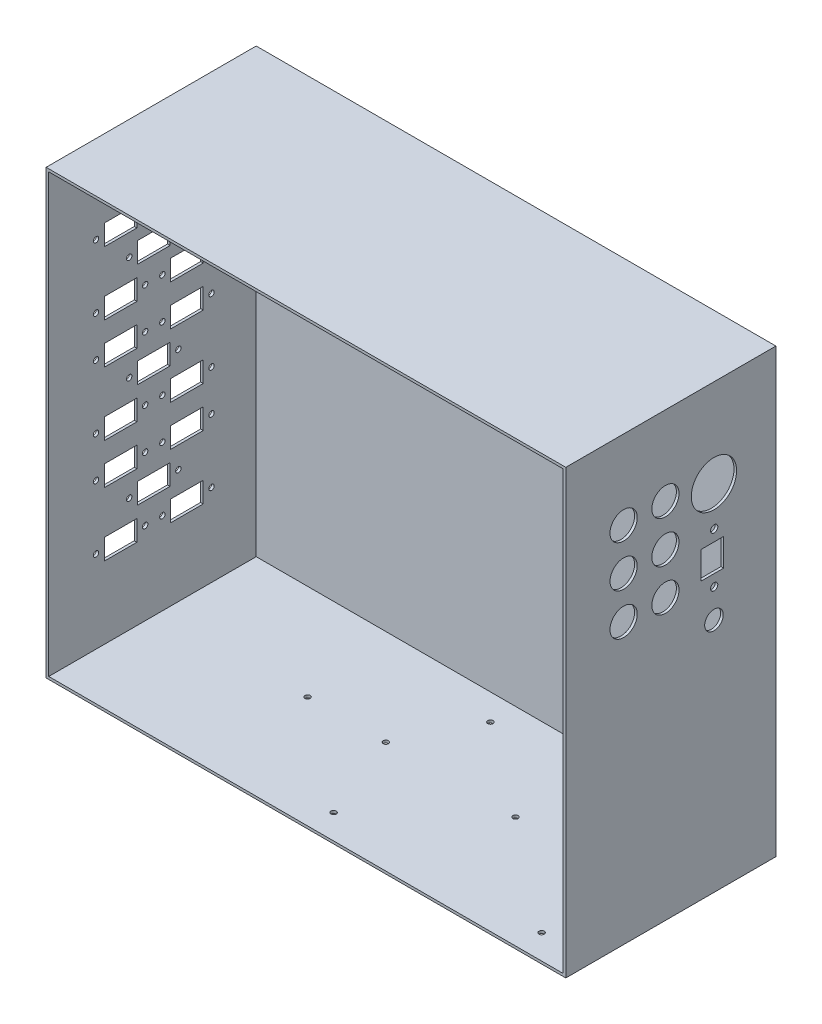
SolidWorks part; units mm, degrees
ref_plane "Front Plane" through (0, 0, 0) normal (0, 0, 1) x (1, 0, 0)
ref_plane "Top Plane" through (0, 0, 0) normal (0, 1, 0) x (1, 0, 0)
ref_plane "Right Plane" through (0, 0, 0) normal (1, 0, 0) x (0, 0, -1)
sketch "Sketch2" plane through (0, 0, 0) normal (0, 0, 1) x (1, 0, 0)
  line L1 (-149.225, 127) -> (149.225, 127)
  line L2 (-149.225, 127) -> (-149.225, -127)
  line L3 (-149.225, -127) -> (149.225, -127)
  line L4 (149.225, 127) -> (149.225, -127)
  line L5 (-149.225, 127) -> (149.225, -127) construction
  line L6 (-149.225, -127) -> (149.225, 127) construction
  point P0 (0, 0)
  dimension "D1" = 298.45
  dimension "D2" = 254
extrude "Boss-Extrude1" add sketch "Sketch2" along normal blind 120.65
shell "Shell1" thickness 1.5 removed face at (0, 0, 120.65)
sketch "Sketch3" plane through (149.225, 0, 0) normal (1, 0, 0) x (0, 0, -1)
  line L0 (-40.4352, 50.2841) -> (-40.4352, 57.3961) construction
  line L1 (-24.3484, 28.5671) -> (-24.2403, 50.2841) construction
  line L2 (-101.6, 95.7164) -> (-19.05, 95.7164) construction
  line L3 (-101.6, 95.7164) -> (-101.6, -88.9) construction
  line L4 (-101.6, -88.9) -> (-19.05, -88.9) construction
  line L5 (-19.05, 95.7164) -> (-19.05, -88.9) construction
  line L6 (-24.3484, 28.5671) -> (-30.4022, 28.5671) construction
  line L7 (-46.489, 28.5671) -> (-46.5749, 50.2841) construction
  line L8 (-24.2403, 50.2841) -> (-30.4022, 50.2841) construction
  line L9 (-30.4022, 50.2841) -> (-30.4022, 57.4161) construction
  line L10 (-40.4352, 28.5671) -> (-46.489, 28.5671) construction
  line L11 (-40.4352, 21.4551) -> (-40.4352, 28.5671) construction
  line L12 (-40.4352, 21.4551) -> (-30.4022, 21.4551) construction
  line L13 (-30.4022, 21.4551) -> (-30.4022, 28.5671) construction
  line L14 (-40.4352, 57.3961) -> (-30.4022, 57.4161) construction
  line L15 (-40.4352, 50.2841) -> (-46.5749, 50.2841) construction
  line L16 (-46.532, 39.4256) -> (-24.2943, 39.4256) construction
  line L17 (-35.4187, 23.6) -> (-35.4187, 57.4061) construction
  line L18 (-43.0873, 31.5516) -> (-43.0873, 47.2996)
  line L19 (-43.0873, 31.5516) -> (-30.0063, 31.5516)
  line L20 (-30.0063, 31.5516) -> (-30.0063, 47.2996)
  line L21 (-43.0873, 47.2996) -> (-30.0063, 47.2996)
  line L24 (-120.65, -127) -> (-120.65, 127) construction
  line L25 (-120.65, -127) -> (0, -127) construction
  circle A0 centre (-87.4395, 33.5559) radius 7.8105
  circle A1 centre (-63.4395, 33.5559) radius 7.8105
  circle A2 centre (-63.4395, 57.5559) radius 7.8105
  circle A3 centre (-63.4395, 81.5559) radius 7.8105
  circle A4 centre (-87.4395, 57.5559) radius 7.8105
  circle A5 centre (-87.4395, 81.5559) radius 7.8105
  circle A6 centre (-35.4187, 25.0111) radius 2.0638
  circle A7 centre (-35.4187, 53.8401) radius 2.0638
  circle A8 centre (-35.56, 8.5011) radius 5.334
  circle A9 centre (-35.56, 76.3489) radius 13.0175
  point P46 (-35.56, -18.9197)
  point P47 (0, 0)
  dimension "D1" = 15.621
  dimension "D4" = 82.55
  dimension "D5" = 14.1605
  dimension "D7" = 19.3675
  dimension "D10" = 28.829
  dimension "D11" = 6.5405
  dimension "D21" = 16.51
  dimension "D6" = 14.1605
  dimension "D8" = 0.512
  dimension "D9" = 13.081
  dimension "D12" = 21.717
  dimension "D13" = 15.748
  dimension "D14" = 7.6686
  dimension "D15" = 0.285
  dimension "D16" = 10.033
  dimension "D17" = 0.227
  dimension "D18" = 16.51
  dimension "D19" = 19.05
  dimension "D20" = 38.1
  dimension "D22" = 0.115
  dimension "D23" = 6.1397
  dimension "D24" = 16.51
  dimension "D2" = 2
  dimension "D3" = 3
extrude "PT Connector Cutouts" cut sketch "Sketch3" against normal up to next
sketch "Sketch4" plane through (-149.225, 0, 0) normal (-1, 0, 0) x (0, 0, 1)
  line L0 (41.275, 72.2563) -> (41.275, 84.0563) construction
  line L1 (31.925, 84.0563) -> (31.925, 72.2563)
  line L2 (31.925, 84.0563) -> (50.625, 84.0563)
  line L3 (50.625, 84.0563) -> (50.625, 72.2563)
  line L4 (31.925, 72.2563) -> (50.625, 72.2563)
  line L10 (22.225, -88.9) -> (98.425, -88.9) construction
  line L11 (22.225, -88.9) -> (22.225, 88.9) construction
  line L12 (22.225, 88.9) -> (98.425, 88.9) construction
  line L13 (98.425, -88.9) -> (98.425, 88.9) construction
  line L73 (120.65, 127) -> (0, 127) construction
  line L74 (0, 127) -> (0, -127) construction
  line L75 (31.925, 86.0563) -> (27.1625, 84.0563) construction
  line L81 (31.925, 70.2563) -> (50.625, 70.2563) construction
  line L83 (31.925, 86.0563) -> (50.625, 86.0563) construction
  line L84 (50.625, 86.0563) -> (55.3875, 84.0563) construction
  line L85 (31.925, 70.2563) -> (27.1625, 72.2563) construction
  line L86 (50.625, 70.2563) -> (55.3875, 72.2563) construction
  line L87 (31.925, 84.0563) -> (50.625, 84.0563) construction
  line L89 (31.925, 72.2563) -> (50.625, 72.2563) construction
  line L91 (31.925, 84.0563) -> (50.625, 84.0563) construction
  line L92 (24.275, 72.2563) -> (24.275, 84.0563) construction
  line L93 (24.275, 72.2563) -> (27.1625, 72.2563) construction
  line L94 (58.275, 72.2563) -> (58.275, 84.0563) construction
  line L95 (24.275, 84.0563) -> (27.1625, 84.0563) construction
  line L98 (55.3875, 84.0563) -> (58.275, 84.0563) construction
  line L99 (55.3875, 72.2563) -> (58.275, 72.2563) construction
  line L100 (31.925, 72.2563) -> (50.625, 72.2563) construction
  line L170 (120.65, -127) -> (0, -127) construction
  line L171 (70.025, 84.0563) -> (70.025, 72.2563)
  line L172 (70.025, 84.0563) -> (88.725, 84.0563)
  line L173 (88.725, 84.0563) -> (88.725, 72.2563)
  line L174 (70.025, 72.2563) -> (88.725, 72.2563)
  line L175 (79.375, 72.2563) -> (79.375, 84.0563) construction
  line L176 (70.025, 86.0563) -> (65.2625, 84.0563) construction
  line L177 (70.025, 70.2563) -> (88.725, 70.2563) construction
  line L178 (70.025, 86.0563) -> (88.725, 86.0563) construction
  line L179 (88.725, 86.0563) -> (93.4875, 84.0563) construction
  line L180 (70.025, 70.2563) -> (65.2625, 72.2563) construction
  line L181 (88.725, 70.2563) -> (93.4875, 72.2563) construction
  line L182 (70.025, 84.0563) -> (88.725, 84.0563) construction
  line L183 (70.025, 72.2563) -> (88.725, 72.2563) construction
  line L184 (70.025, 84.0563) -> (88.725, 84.0563) construction
  line L185 (62.375, 72.2563) -> (62.375, 84.0563) construction
  line L186 (62.375, 72.2563) -> (65.2625, 72.2563) construction
  line L187 (96.375, 72.2563) -> (96.375, 84.0563) construction
  line L188 (62.375, 84.0563) -> (65.2625, 84.0563) construction
  line L189 (93.4875, 84.0563) -> (96.375, 84.0563) construction
  line L190 (93.4875, 72.2563) -> (96.375, 72.2563) construction
  line L191 (70.025, 72.2563) -> (88.725, 72.2563) construction
  line L213 (70.025, 47.5438) -> (70.025, 35.7438)
  line L214 (70.025, 47.5438) -> (88.725, 47.5438)
  line L215 (88.725, 47.5438) -> (88.725, 35.7438)
  line L216 (70.025, 35.7438) -> (88.725, 35.7438)
  line L217 (79.375, 35.7438) -> (79.375, 47.5438) construction
  line L218 (70.025, 49.5438) -> (65.2625, 47.5438) construction
  line L219 (70.025, 33.7438) -> (88.725, 33.7438) construction
  line L220 (70.025, 49.5438) -> (88.725, 49.5438) construction
  line L221 (88.725, 49.5438) -> (93.4875, 47.5438) construction
  line L222 (70.025, 33.7438) -> (65.2625, 35.7438) construction
  line L223 (88.725, 33.7438) -> (93.4875, 35.7438) construction
  line L224 (70.025, 47.5438) -> (88.725, 47.5438) construction
  line L225 (70.025, 35.7438) -> (88.725, 35.7438) construction
  line L226 (70.025, 47.5438) -> (88.725, 47.5438) construction
  line L227 (62.375, 35.7438) -> (62.375, 47.5438) construction
  line L228 (62.375, 35.7438) -> (65.2625, 35.7438) construction
  line L229 (96.375, 35.7438) -> (96.375, 47.5438) construction
  line L230 (62.375, 47.5438) -> (65.2625, 47.5438) construction
  line L231 (93.4875, 47.5438) -> (96.375, 47.5438) construction
  line L232 (93.4875, 35.7438) -> (96.375, 35.7438) construction
  line L233 (70.025, 35.7438) -> (88.725, 35.7438) construction
  line L234 (70.025, 24.1563) -> (70.025, 12.3563)
  line L235 (70.025, 24.1563) -> (88.725, 24.1563)
  line L236 (88.725, 24.1563) -> (88.725, 12.3563)
  line L237 (70.025, 12.3563) -> (88.725, 12.3563)
  line L238 (79.375, 12.3563) -> (79.375, 24.1563) construction
  line L239 (70.025, 26.1563) -> (65.2625, 24.1563) construction
  line L240 (70.025, 10.3563) -> (88.725, 10.3563) construction
  line L241 (70.025, 26.1563) -> (88.725, 26.1563) construction
  line L242 (88.725, 26.1563) -> (93.4875, 24.1563) construction
  line L243 (70.025, 10.3563) -> (65.2625, 12.3563) construction
  line L244 (88.725, 10.3563) -> (93.4875, 12.3563) construction
  line L245 (70.025, 24.1563) -> (88.725, 24.1563) construction
  line L246 (70.025, 12.3563) -> (88.725, 12.3563) construction
  line L247 (70.025, 24.1563) -> (88.725, 24.1563) construction
  line L248 (62.375, 12.3563) -> (62.375, 24.1563) construction
  line L249 (62.375, 12.3563) -> (65.2625, 12.3563) construction
  line L250 (96.375, 12.3563) -> (96.375, 24.1563) construction
  line L251 (62.375, 24.1563) -> (65.2625, 24.1563) construction
  line L252 (93.4875, 24.1563) -> (96.375, 24.1563) construction
  line L253 (93.4875, 12.3563) -> (96.375, 12.3563) construction
  line L254 (70.025, 12.3563) -> (88.725, 12.3563) construction
  line L276 (70.025, -12.3562) -> (70.025, -24.1562)
  line L277 (70.025, -12.3562) -> (88.725, -12.3562)
  line L278 (88.725, -12.3562) -> (88.725, -24.1562)
  line L279 (70.025, -24.1562) -> (88.725, -24.1562)
  line L280 (79.375, -24.1562) -> (79.375, -12.3562) construction
  line L281 (70.025, -10.3562) -> (65.2625, -12.3562) construction
  line L282 (70.025, -26.1562) -> (88.725, -26.1562) construction
  line L283 (70.025, -10.3562) -> (88.725, -10.3562) construction
  line L284 (88.725, -10.3562) -> (93.4875, -12.3562) construction
  line L285 (70.025, -26.1562) -> (65.2625, -24.1562) construction
  line L286 (88.725, -26.1562) -> (93.4875, -24.1562) construction
  line L287 (70.025, -12.3562) -> (88.725, -12.3562) construction
  line L288 (70.025, -24.1562) -> (88.725, -24.1562) construction
  line L289 (70.025, -12.3562) -> (88.725, -12.3562) construction
  line L290 (62.375, -24.1562) -> (62.375, -12.3562) construction
  line L291 (62.375, -24.1562) -> (65.2625, -24.1562) construction
  line L292 (96.375, -24.1562) -> (96.375, -12.3562) construction
  line L293 (62.375, -12.3562) -> (65.2625, -12.3562) construction
  line L294 (93.4875, -12.3562) -> (96.375, -12.3562) construction
  line L295 (93.4875, -24.1562) -> (96.375, -24.1562) construction
  line L296 (70.025, -24.1562) -> (88.725, -24.1562) construction
  line L297 (70.025, -35.7437) -> (70.025, -47.5437)
  line L298 (70.025, -35.7437) -> (88.725, -35.7437)
  line L299 (88.725, -35.7437) -> (88.725, -47.5437)
  line L300 (70.025, -47.5437) -> (88.725, -47.5437)
  line L301 (79.375, -47.5437) -> (79.375, -35.7437) construction
  line L302 (70.025, -33.7437) -> (65.2625, -35.7437) construction
  line L303 (70.025, -49.5437) -> (88.725, -49.5437) construction
  line L304 (70.025, -33.7437) -> (88.725, -33.7437) construction
  line L305 (88.725, -33.7437) -> (93.4875, -35.7437) construction
  line L306 (70.025, -49.5437) -> (65.2625, -47.5437) construction
  line L307 (88.725, -49.5437) -> (93.4875, -47.5437) construction
  line L308 (70.025, -35.7437) -> (88.725, -35.7437) construction
  line L309 (70.025, -47.5437) -> (88.725, -47.5437) construction
  line L310 (70.025, -35.7437) -> (88.725, -35.7437) construction
  line L311 (62.375, -47.5437) -> (62.375, -35.7437) construction
  line L312 (62.375, -47.5437) -> (65.2625, -47.5437) construction
  line L313 (96.375, -47.5437) -> (96.375, -35.7437) construction
  line L314 (62.375, -35.7437) -> (65.2625, -35.7437) construction
  line L315 (93.4875, -35.7437) -> (96.375, -35.7437) construction
  line L316 (93.4875, -47.5437) -> (96.375, -47.5437) construction
  line L317 (70.025, -47.5437) -> (88.725, -47.5437) construction
  line L339 (70.025, -72.2562) -> (70.025, -84.0562)
  line L340 (70.025, -72.2562) -> (88.725, -72.2562)
  line L341 (88.725, -72.2562) -> (88.725, -84.0562)
  line L342 (70.025, -84.0562) -> (88.725, -84.0562)
  line L343 (79.375, -84.0562) -> (79.375, -72.2562) construction
  line L344 (70.025, -70.2562) -> (65.2625, -72.2562) construction
  line L345 (70.025, -86.0562) -> (88.725, -86.0562) construction
  line L346 (70.025, -70.2562) -> (88.725, -70.2562) construction
  line L347 (88.725, -70.2562) -> (93.4875, -72.2562) construction
  line L348 (70.025, -86.0562) -> (65.2625, -84.0562) construction
  line L349 (88.725, -86.0562) -> (93.4875, -84.0562) construction
  line L350 (70.025, -72.2562) -> (88.725, -72.2562) construction
  line L351 (70.025, -84.0562) -> (88.725, -84.0562) construction
  line L352 (70.025, -72.2562) -> (88.725, -72.2562) construction
  line L353 (62.375, -84.0562) -> (62.375, -72.2562) construction
  line L354 (62.375, -84.0562) -> (65.2625, -84.0562) construction
  line L355 (96.375, -84.0562) -> (96.375, -72.2562) construction
  line L356 (62.375, -72.2562) -> (65.2625, -72.2562) construction
  line L357 (93.4875, -72.2562) -> (96.375, -72.2562) construction
  line L358 (93.4875, -84.0562) -> (96.375, -84.0562) construction
  line L359 (70.025, -84.0562) -> (88.725, -84.0562) construction
  line L360 (50.975, 65.8) -> (50.975, 54)
  line L361 (50.975, 65.8) -> (69.675, 65.8)
  line L362 (69.675, 65.8) -> (69.675, 54)
  line L363 (50.975, 54) -> (69.675, 54)
  line L364 (60.325, 54) -> (60.325, 65.8) construction
  line L365 (50.975, 67.8) -> (46.2125, 65.8) construction
  line L366 (50.975, 52) -> (69.675, 52) construction
  line L367 (50.975, 67.8) -> (69.675, 67.8) construction
  line L368 (69.675, 67.8) -> (74.4375, 65.8) construction
  line L369 (50.975, 52) -> (46.2125, 54) construction
  line L370 (69.675, 52) -> (74.4375, 54) construction
  line L371 (50.975, 65.8) -> (69.675, 65.8) construction
  line L372 (50.975, 54) -> (69.675, 54) construction
  line L373 (50.975, 65.8) -> (69.675, 65.8) construction
  line L374 (43.325, 54) -> (43.325, 65.8) construction
  line L375 (43.325, 54) -> (46.2125, 54) construction
  line L376 (77.325, 54) -> (77.325, 65.8) construction
  line L377 (43.325, 65.8) -> (46.2125, 65.8) construction
  line L378 (74.4375, 65.8) -> (77.325, 65.8) construction
  line L379 (74.4375, 54) -> (77.325, 54) construction
  line L380 (50.975, 54) -> (69.675, 54) construction
  line L381 (31.925, 47.5438) -> (31.925, 35.7438)
  line L382 (31.925, 47.5438) -> (50.625, 47.5438)
  line L383 (50.625, 47.5438) -> (50.625, 35.7438)
  line L384 (31.925, 35.7438) -> (50.625, 35.7438)
  line L385 (41.275, 35.7438) -> (41.275, 47.5438) construction
  line L386 (31.925, 49.5438) -> (27.1625, 47.5438) construction
  line L387 (31.925, 33.7438) -> (50.625, 33.7438) construction
  line L388 (31.925, 49.5438) -> (50.625, 49.5438) construction
  line L389 (50.625, 49.5438) -> (55.3875, 47.5438) construction
  line L390 (31.925, 33.7438) -> (27.1625, 35.7438) construction
  line L391 (50.625, 33.7438) -> (55.3875, 35.7438) construction
  line L392 (31.925, 47.5438) -> (50.625, 47.5438) construction
  line L393 (31.925, 35.7438) -> (50.625, 35.7438) construction
  line L394 (31.925, 47.5438) -> (50.625, 47.5438) construction
  line L395 (24.275, 35.7438) -> (24.275, 47.5438) construction
  line L396 (24.275, 35.7438) -> (27.1625, 35.7438) construction
  line L397 (58.275, 35.7438) -> (58.275, 47.5438) construction
  line L398 (24.275, 47.5438) -> (27.1625, 47.5438) construction
  line L399 (55.3875, 47.5438) -> (58.275, 47.5438) construction
  line L400 (55.3875, 35.7438) -> (58.275, 35.7438) construction
  line L401 (31.925, 35.7438) -> (50.625, 35.7438) construction
  line L402 (31.925, 24.1563) -> (31.925, 12.3563)
  line L403 (31.925, 24.1563) -> (50.625, 24.1563)
  line L404 (50.625, 24.1563) -> (50.625, 12.3563)
  line L405 (31.925, 12.3563) -> (50.625, 12.3563)
  line L406 (41.275, 12.3563) -> (41.275, 24.1563) construction
  line L407 (31.925, 26.1563) -> (27.1625, 24.1563) construction
  line L408 (31.925, 10.3563) -> (50.625, 10.3563) construction
  line L409 (31.925, 26.1563) -> (50.625, 26.1563) construction
  line L410 (50.625, 26.1563) -> (55.3875, 24.1563) construction
  line L411 (31.925, 10.3563) -> (27.1625, 12.3563) construction
  line L412 (50.625, 10.3563) -> (55.3875, 12.3563) construction
  line L413 (31.925, 24.1563) -> (50.625, 24.1563) construction
  line L414 (31.925, 12.3563) -> (50.625, 12.3563) construction
  line L415 (31.925, 24.1563) -> (50.625, 24.1563) construction
  line L416 (24.275, 12.3563) -> (24.275, 24.1563) construction
  line L417 (24.275, 12.3563) -> (27.1625, 12.3563) construction
  line L418 (58.275, 12.3563) -> (58.275, 24.1563) construction
  line L419 (24.275, 24.1563) -> (27.1625, 24.1563) construction
  line L420 (55.3875, 24.1563) -> (58.275, 24.1563) construction
  line L421 (55.3875, 12.3563) -> (58.275, 12.3563) construction
  line L422 (31.925, 12.3563) -> (50.625, 12.3563) construction
  line L423 (50.975, 5.9) -> (50.975, -5.9)
  line L424 (50.975, 5.9) -> (69.675, 5.9)
  line L425 (69.675, 5.9) -> (69.675, -5.9)
  line L426 (50.975, -5.9) -> (69.675, -5.9)
  line L427 (60.325, -5.9) -> (60.325, 5.9) construction
  line L428 (50.975, 7.9) -> (46.2125, 5.9) construction
  line L429 (50.975, -7.9) -> (69.675, -7.9) construction
  line L430 (50.975, 7.9) -> (69.675, 7.9) construction
  line L431 (69.675, 7.9) -> (74.4375, 5.9) construction
  line L432 (50.975, -7.9) -> (46.2125, -5.9) construction
  line L433 (69.675, -7.9) -> (74.4375, -5.9) construction
  line L434 (50.975, 5.9) -> (69.675, 5.9) construction
  line L435 (50.975, -5.9) -> (69.675, -5.9) construction
  line L436 (50.975, 5.9) -> (69.675, 5.9) construction
  line L437 (43.325, -5.9) -> (43.325, 5.9) construction
  line L438 (43.325, -5.9) -> (46.2125, -5.9) construction
  line L439 (77.325, -5.9) -> (77.325, 5.9) construction
  line L440 (43.325, 5.9) -> (46.2125, 5.9) construction
  line L441 (74.4375, 5.9) -> (77.325, 5.9) construction
  line L442 (74.4375, -5.9) -> (77.325, -5.9) construction
  line L443 (50.975, -5.9) -> (69.675, -5.9) construction
  line L444 (31.925, -12.3562) -> (31.925, -24.1562)
  line L445 (31.925, -12.3562) -> (50.625, -12.3562)
  line L446 (50.625, -12.3562) -> (50.625, -24.1562)
  line L447 (31.925, -24.1562) -> (50.625, -24.1562)
  line L448 (41.275, -24.1562) -> (41.275, -12.3562) construction
  line L449 (31.925, -10.3562) -> (27.1625, -12.3562) construction
  line L450 (31.925, -26.1562) -> (50.625, -26.1562) construction
  line L451 (31.925, -10.3562) -> (50.625, -10.3562) construction
  line L452 (50.625, -10.3562) -> (55.3875, -12.3562) construction
  line L453 (31.925, -26.1562) -> (27.1625, -24.1562) construction
  line L454 (50.625, -26.1562) -> (55.3875, -24.1562) construction
  line L455 (31.925, -12.3562) -> (50.625, -12.3562) construction
  line L456 (31.925, -24.1562) -> (50.625, -24.1562) construction
  line L457 (31.925, -12.3562) -> (50.625, -12.3562) construction
  line L458 (24.275, -24.1562) -> (24.275, -12.3562) construction
  line L459 (24.275, -24.1562) -> (27.1625, -24.1562) construction
  line L460 (58.275, -24.1562) -> (58.275, -12.3562) construction
  line L461 (24.275, -12.3562) -> (27.1625, -12.3562) construction
  line L462 (55.3875, -12.3562) -> (58.275, -12.3562) construction
  line L463 (55.3875, -24.1562) -> (58.275, -24.1562) construction
  line L464 (31.925, -24.1562) -> (50.625, -24.1562) construction
  line L465 (31.925, -35.7437) -> (31.925, -47.5437)
  line L466 (31.925, -35.7437) -> (50.625, -35.7437)
  line L467 (50.625, -35.7437) -> (50.625, -47.5437)
  line L468 (31.925, -47.5437) -> (50.625, -47.5437)
  line L469 (41.275, -47.5437) -> (41.275, -35.7437) construction
  line L470 (31.925, -33.7437) -> (27.1625, -35.7437) construction
  line L471 (31.925, -49.5437) -> (50.625, -49.5437) construction
  line L472 (31.925, -33.7437) -> (50.625, -33.7437) construction
  line L473 (50.625, -33.7437) -> (55.3875, -35.7437) construction
  line L474 (31.925, -49.5437) -> (27.1625, -47.5437) construction
  line L475 (50.625, -49.5437) -> (55.3875, -47.5437) construction
  line L476 (31.925, -35.7437) -> (50.625, -35.7437) construction
  line L477 (31.925, -47.5437) -> (50.625, -47.5437) construction
  line L478 (31.925, -35.7437) -> (50.625, -35.7437) construction
  line L479 (24.275, -47.5437) -> (24.275, -35.7437) construction
  line L480 (24.275, -47.5437) -> (27.1625, -47.5437) construction
  line L481 (58.275, -47.5437) -> (58.275, -35.7437) construction
  line L482 (24.275, -35.7437) -> (27.1625, -35.7437) construction
  line L483 (55.3875, -35.7437) -> (58.275, -35.7437) construction
  line L484 (55.3875, -47.5437) -> (58.275, -47.5437) construction
  line L485 (31.925, -47.5437) -> (50.625, -47.5437) construction
  line L486 (50.975, -54) -> (50.975, -65.8)
  line L487 (50.975, -54) -> (69.675, -54)
  line L488 (69.675, -54) -> (69.675, -65.8)
  line L489 (50.975, -65.8) -> (69.675, -65.8)
  line L490 (60.325, -65.8) -> (60.325, -54) construction
  line L491 (50.975, -52) -> (46.2125, -54) construction
  line L492 (50.975, -67.8) -> (69.675, -67.8) construction
  line L493 (50.975, -52) -> (69.675, -52) construction
  line L494 (69.675, -52) -> (74.4375, -54) construction
  line L495 (50.975, -67.8) -> (46.2125, -65.8) construction
  line L496 (69.675, -67.8) -> (74.4375, -65.8) construction
  line L497 (50.975, -54) -> (69.675, -54) construction
  line L498 (50.975, -65.8) -> (69.675, -65.8) construction
  line L499 (50.975, -54) -> (69.675, -54) construction
  line L500 (43.325, -65.8) -> (43.325, -54) construction
  line L501 (43.325, -65.8) -> (46.2125, -65.8) construction
  line L502 (77.325, -65.8) -> (77.325, -54) construction
  line L503 (43.325, -54) -> (46.2125, -54) construction
  line L504 (74.4375, -54) -> (77.325, -54) construction
  line L505 (74.4375, -65.8) -> (77.325, -65.8) construction
  line L506 (50.975, -65.8) -> (69.675, -65.8) construction
  line L507 (31.925, -72.2562) -> (31.925, -84.0562)
  line L508 (31.925, -72.2562) -> (50.625, -72.2562)
  line L509 (50.625, -72.2562) -> (50.625, -84.0562)
  line L510 (31.925, -84.0562) -> (50.625, -84.0562)
  line L511 (41.275, -84.0562) -> (41.275, -72.2562) construction
  line L512 (31.925, -70.2562) -> (27.1625, -72.2562) construction
  line L513 (31.925, -86.0562) -> (50.625, -86.0562) construction
  line L514 (31.925, -70.2562) -> (50.625, -70.2562) construction
  line L515 (50.625, -70.2562) -> (55.3875, -72.2562) construction
  line L516 (31.925, -86.0562) -> (27.1625, -84.0562) construction
  line L517 (50.625, -86.0562) -> (55.3875, -84.0562) construction
  line L518 (31.925, -72.2562) -> (50.625, -72.2562) construction
  line L519 (31.925, -84.0562) -> (50.625, -84.0562) construction
  line L520 (31.925, -72.2562) -> (50.625, -72.2562) construction
  line L521 (24.275, -84.0562) -> (24.275, -72.2562) construction
  line L522 (24.275, -84.0562) -> (27.1625, -84.0562) construction
  line L523 (58.275, -84.0562) -> (58.275, -72.2562) construction
  line L524 (24.275, -72.2562) -> (27.1625, -72.2562) construction
  line L525 (55.3875, -72.2562) -> (58.275, -72.2562) construction
  line L526 (55.3875, -84.0562) -> (58.275, -84.0562) construction
  line L527 (31.925, -84.0562) -> (50.625, -84.0562) construction
  circle A0 centre (55.3875, 78.1563) radius 1.55
  circle A1 centre (27.1625, 78.1563) radius 1.55
  circle A2 centre (93.4875, 78.1563) radius 1.55
  circle A3 centre (65.2625, 78.1563) radius 1.55
  circle A6 centre (93.4875, 41.6438) radius 1.55
  circle A7 centre (65.2625, 41.6438) radius 1.55
  circle A8 centre (93.4875, 18.2563) radius 1.55
  circle A9 centre (65.2625, 18.2563) radius 1.55
  circle A12 centre (93.4875, -18.2562) radius 1.55
  circle A13 centre (65.2625, -18.2562) radius 1.55
  circle A14 centre (93.4875, -41.6437) radius 1.55
  circle A15 centre (65.2625, -41.6437) radius 1.55
  circle A18 centre (93.4875, -78.1562) radius 1.55
  circle A19 centre (65.2625, -78.1562) radius 1.55
  circle A20 centre (74.4375, 59.9) radius 1.55
  circle A21 centre (46.2125, 59.9) radius 1.55
  circle A22 centre (55.3875, 41.6438) radius 1.55
  circle A23 centre (27.1625, 41.6438) radius 1.55
  circle A24 centre (55.3875, 18.2563) radius 1.55
  circle A25 centre (27.1625, 18.2563) radius 1.55
  circle A26 centre (74.4375, 0) radius 1.55
  circle A27 centre (46.2125, 0) radius 1.55
  circle A28 centre (55.3875, -18.2562) radius 1.55
  circle A29 centre (27.1625, -18.2562) radius 1.55
  circle A30 centre (55.3875, -41.6437) radius 1.55
  circle A31 centre (27.1625, -41.6437) radius 1.55
  circle A32 centre (74.4375, -59.9) radius 1.55
  circle A33 centre (46.2125, -59.9) radius 1.55
  circle A34 centre (55.3875, -78.1562) radius 1.55
  circle A35 centre (27.1625, -78.1562) radius 1.55
  point P0 (41.275, 78.1563)
  point P10 (41.275, 78.1563)
  point P14 (79.375, 78.1563)
  point P30 (79.375, 78.1563)
  point P32 (79.375, 78.1563)
  point P33 (79.375, 78.1563)
  point P37 (79.375, 78.1563)
  point P76 (79.375, 41.6438)
  point P86 (79.375, 41.6438)
  point P88 (79.375, 41.6438)
  point P89 (79.375, 41.6438)
  point P93 (79.375, 41.6438)
  point P103 (79.375, 18.2563)
  point P113 (79.375, 18.2563)
  point P115 (79.375, 18.2563)
  point P116 (79.375, 18.2563)
  point P120 (79.375, 18.2563)
  point P141 (41.275, 78.1563)
  point P142 (41.275, 78.1563)
  point P146 (41.275, 78.1563)
  point P174 (79.375, -18.2562)
  point P184 (79.375, -18.2562)
  point P186 (79.375, -18.2562)
  point P187 (79.375, -18.2562)
  point P191 (79.375, -18.2562)
  point P201 (79.375, -41.6437)
  point P211 (79.375, -41.6437)
  point P213 (79.375, -41.6437)
  point P214 (79.375, -41.6437)
  point P218 (79.375, -41.6437)
  point P255 (79.375, -78.1562)
  point P265 (79.375, -78.1562)
  point P267 (79.375, -78.1562)
  point P268 (79.375, -78.1562)
  point P272 (79.375, -78.1562)
  point P282 (60.325, 59.9)
  point P292 (60.325, 59.9)
  point P294 (60.325, 59.9)
  point P295 (60.325, 59.9)
  point P299 (60.325, 59.9)
  point P309 (41.275, 41.6438)
  point P319 (41.275, 41.6438)
  point P321 (41.275, 41.6438)
  point P322 (41.275, 41.6438)
  point P326 (41.275, 41.6438)
  point P336 (41.275, 18.2563)
  point P346 (41.275, 18.2563)
  point P348 (41.275, 18.2563)
  point P349 (41.275, 18.2563)
  point P353 (41.275, 18.2563)
  point P363 (60.325, 0)
  point P373 (60.325, 0)
  point P375 (60.325, 0)
  point P376 (60.325, 0)
  point P380 (60.325, 0)
  point P390 (41.275, -18.2562)
  point P400 (41.275, -18.2562)
  point P402 (41.275, -18.2562)
  point P403 (41.275, -18.2562)
  point P407 (41.275, -18.2562)
  point P417 (41.275, -41.6437)
  point P427 (41.275, -41.6437)
  point P429 (41.275, -41.6437)
  point P430 (41.275, -41.6437)
  point P434 (41.275, -41.6437)
  point P444 (60.325, -59.9)
  point P454 (60.325, -59.9)
  point P456 (60.325, -59.9)
  point P457 (60.325, -59.9)
  point P461 (60.325, -59.9)
  point P471 (41.275, -78.1562)
  point P481 (41.275, -78.1562)
  point P483 (41.275, -78.1562)
  point P484 (41.275, -78.1562)
  point P488 (41.275, -78.1562)
  dimension "D1" = 18.7
  dimension "D4" = 4.7625
  dimension "D5" = 177.8
  dimension "D6" = 76.2
  dimension "D9" = 38.1
  dimension "D10" = 22.225
  dimension "D11" = 34
  dimension "D12" = 15.8
  dimension "D13" = 18.7
  dimension "D14" = 4.7625
extrude "Solenoid Connector Cutouts" cut sketch "Sketch4" against normal up to next (1.5 mm away)
sketch "Punchout Panel" plane through (-149.225, 0, 0) normal (-1, 0, 0) x (0, 0, 1)
  line L1 (98.425, 88.9) -> (22.225, 88.9) construction
  line L2 (98.425, 88.9) -> (98.425, -88.9) construction
  line L3 (98.425, -88.9) -> (22.225, -88.9) construction
  line L4 (22.225, 88.9) -> (22.225, -88.9) construction
  point P0 (60.325, 0)
sketch "Sketch5" plane through (0, -127, 127) normal (0, 1, 0) x (-1, 0, 0)
  line L1 (-126.2359, -15.4623) -> (-51.2359, -15.4623) construction
  line L2 (-126.2359, -15.4623) -> (-126.2359, -115.4623) construction
  line L3 (-126.2359, -115.4623) -> (-51.2359, -115.4623) construction
  line L4 (-51.2359, -15.4623) -> (-51.2359, -115.4623) construction
  line L5 (-6.7859, -15.4623) -> (68.2141, -15.4623) construction
  line L6 (-6.7859, -15.4623) -> (-6.7859, -115.4623) construction
  line L7 (-6.7859, -115.4623) -> (68.2141, -115.4623) construction
  line L8 (68.2141, -15.4623) -> (68.2141, -115.4623) construction
  circle A0 centre (-121.2359, -20.4623) radius 1.524
  circle A4 centre (-56.2359, -70.4623) radius 1.524
  circle A5 centre (-121.2359, -110.4623) radius 1.524
  circle A7 centre (-101.2359, -70.4623) radius 1.524
  circle A8 centre (-1.7859, -20.4623) radius 1.524
  circle A9 centre (63.2141, -70.4623) radius 1.524
  circle A10 centre (-1.7859, -110.4623) radius 1.524
  circle A11 centre (18.2141, -70.4623) radius 1.524
  dimension "D3" = 3.048
  dimension "D6" = 3.048
  dimension "D8" = 3.048
  dimension "D9" = 3.048
  dimension "D16" = 3.048
  dimension "D19" = 3.048
  dimension "D21" = 3.048
  dimension "D22" = 3.048
  dimension "D1" = 75
  dimension "D2" = 100
  dimension "D4" = 5
  dimension "D5" = 5
  dimension "D7" = 5
  dimension "D10" = 55
  dimension "D11" = 45
  dimension "D12" = 5
  dimension "D13" = 5
  dimension "D14" = 75
  dimension "D15" = 100
  dimension "D17" = 5
  dimension "D18" = 5
  dimension "D20" = 5
  dimension "D23" = 55
  dimension "D24" = 45
  dimension "D25" = 5
  dimension "D26" = 5
  dimension "D27" = 44.45
extrude "PCB Mounting Holes" cut sketch "Sketch5" along normal up to surface (1.5 mm away) up to face at (0, -125.5, 61.075)
